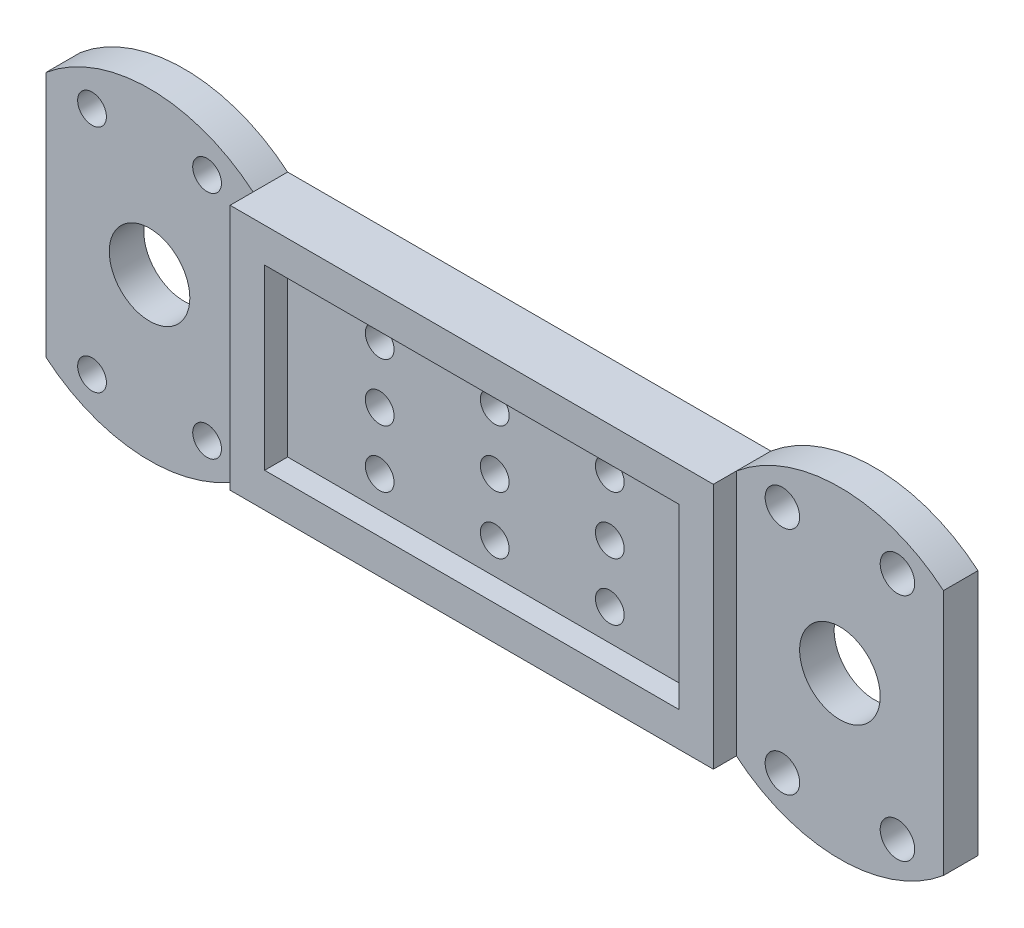
SolidWorks part; units mm, degrees
ref_plane "Front Plane" through (0, 0, 0) normal (0, 0, 1) x (1, 0, 0)
ref_plane "Top Plane" through (0, 0, 0) normal (0, 1, 0) x (1, 0, 0)
ref_plane "Right Plane" through (0, 0, 0) normal (1, 0, 0) x (0, 0, -1)
sketch "Sketch1" plane through (0, 0, 0) normal (0, 0, 1) x (1, 0, 0)
  line L0 (-9, 10.7238) -> (-9, -10.7238)
  line L1 (9, -10.7238) -> (51, -10.7238)
  line L2 (-9, 0) -> (9, 0) construction
  line L3 (-5, 10) -> (5, -10) construction
  line L4 (-5, -10) -> (5, 10) construction
  line L5 (9, 10.7238) -> (51, 10.7238)
  line L6 (0, 0) -> (60, 0) construction
  line L7 (69, 10.7238) -> (69, -10.7238)
  line L8 (55, 10) -> (65, -10) construction
  line L9 (65, 10) -> (55, -10) construction
  arc A0 (9, 10.7238) -> (-9, 10.7238) centre (0, 0) ccw
  arc A1 (-9, -10.7238) -> (9, -10.7238) centre (0, 0) ccw
  circle A2 centre (0, 0) radius 3.5
  circle A3 centre (-5, 10) radius 1.25
  circle A4 centre (5, 10) radius 1.25
  circle A5 centre (-5, -10) radius 1.25
  circle A6 centre (5, -10) radius 1.25
  arc A7 (51, -10.7238) -> (69, -10.7238) centre (60, 0) ccw
  arc A8 (69, 10.7238) -> (51, 10.7238) centre (60, 0) ccw
  circle A9 centre (60, 0) radius 3.5
  circle A10 centre (55, 10) radius 1.5
  circle A11 centre (65, 10) radius 1.5
  circle A12 centre (55, -10) radius 1.5
  circle A13 centre (65, -10) radius 1.5
  circle A14 centre (30, 0) radius 1.25
  circle A15 centre (30, 5) radius 1.25
  circle A16 centre (30, -5) radius 1.25
  circle A17 centre (40, 0) radius 1.25
  circle A18 centre (20, 0) radius 1.25
  circle A19 centre (40, 5) radius 1.25
  circle A20 centre (40, -5) radius 1.25
  circle A21 centre (20, -5) radius 1.25
  circle A22 centre (20, 5) radius 1.25
  point P7 (0, 0)
  point P18 (0, 0)
  point P25 (60, 0)
  point P36 (60, 0)
  dimension "D2" = 14
  dimension "D3" = 7
  dimension "D6" = 2.5
  dimension "D8" = 3
  dimension "D11" = 2.5
  dimension "D1" = 18
  dimension "D4" = 20
  dimension "D5" = 10
  dimension "D7" = 60
  dimension "D9" = 10
  dimension "D10" = 20
  dimension "D12" = 5
  dimension "D13" = 10
  dimension "D14" = 10
  dimension "D15" = 5
extrude "Boss-Extrude1" add sketch "Sketch1" along normal blind 3
sketch "Sketch2" plane through (0, 0, 3) normal (0, 0, -1) x (-1, 0, 0)
  line L2 (-9, 10.7238) -> (-51, 10.7238)
  line L3 (-9, 10.7238) -> (-9, -10.7238)
  line L4 (-9, -10.7238) -> (-51, -10.7238)
  line L5 (-51, 10.7238) -> (-51, -10.7238)
  line L6 (-12, 7.7238) -> (-48, 7.7238)
  line L7 (-12, 7.7238) -> (-12, -7.7238)
  line L8 (-12, -7.7238) -> (-48, -7.7238)
  line L9 (-48, 7.7238) -> (-48, -7.7238)
  dimension "D1" = 3
  dimension "D2" = 3
  dimension "D3" = 3
  dimension "D4" = 3
extrude "Boss-Extrude2" add sketch "Sketch2" against normal blind 2
